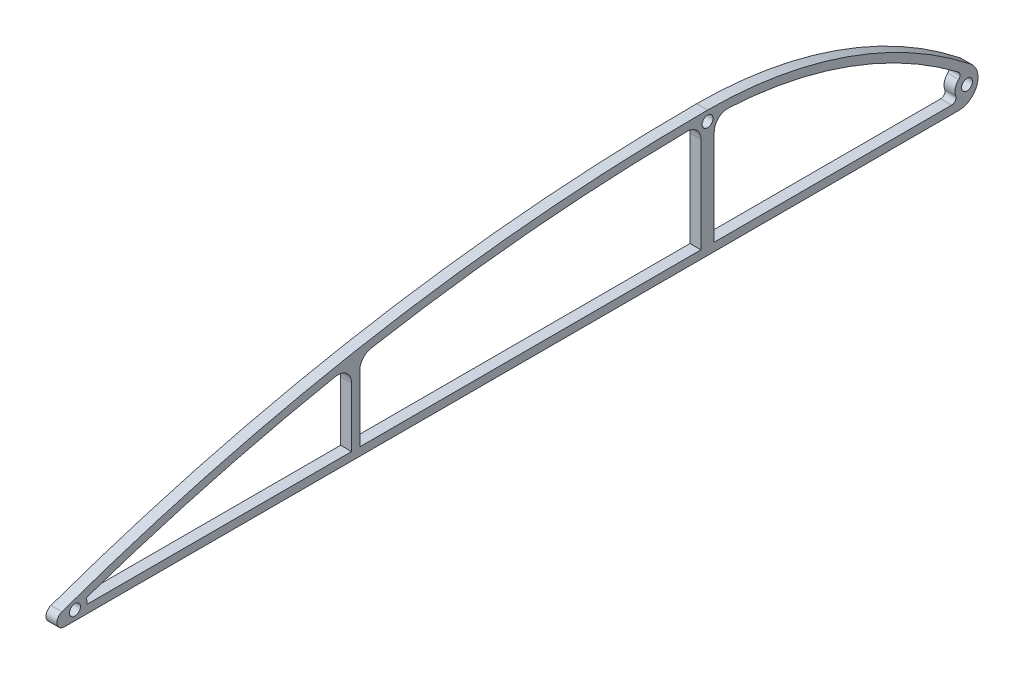
SolidWorks part; units mm, degrees
other "Marquage1"
sketch "Esquisse8" plane through (8, 0, -172.8424) normal (1, 0, 0) x (0, 0, -1)
other "Marquage2"
sketch "Esquisse10" plane through (-6, 20, -172.8424) normal (-0.8365, 0.2588, -0.483) x (-0.5, 0, 0.866)
other "Marquage3"
sketch "Esquisse11" plane through (0, 0, 0) normal (-0.0501, -0.1345, 0.9896) x (0.9942, 0.0873, 0.0622)
ref_plane "Plan de face" through (0, 0, 0) normal (0, 0, 1) x (1, 0, 0)
ref_plane "Plan de dessus" through (0, 0, 0) normal (0, 1, 0) x (1, 0, 0)
ref_plane "Plan de droite" through (0, 0, 0) normal (1, 0, 0) x (0, 0, -1)
sketch "Esquisse2" plane through (0, 0, 0) normal (1, 0, 0) x (0, 0, -1)
  line L0 (0, 0) -> (170.8732, 0)
  arc A1 (173.0499, 6.2408) -> (125, 23) centre (125, -54.2609) ccw
  arc A3 (170.8732, 0) -> (173.0499, 6.2408) centre (170.8732, 3.5) ccw
  arc A4 (125, 23) -> (0, 0) centre (125, -328.1739) ccw
  point P10 (180, 0)
  dimension "D1" = 180
  dimension "D2" = 3.5
  dimension "D3" = 23
  dimension "D4" = 55
extrude "Boss.-Extru.1" add sketch "Esquisse2" along normal blind 2
sketch "Esquisse4" plane through (2, 0, 0) normal (1, 0, 0) x (0, 0, -1)
  line L0 (9.5, 0) -> (9.5, 3.4627) construction
  line L1 (0, 0) -> (9.5, 1.7314) construction
  line L10 (174.369, 3.3283) -> (172.369, 3.3283) construction
  line L11 (0, 0) -> (170.8732, 0) construction
  circle A6 centre (125, 21.2) radius 1
  circle A12 centre (172.369, 3.3283) radius 1
  arc A13 (170.8732, 0) -> (173.0499, 6.2408) centre (170.8732, 3.5) ccw construction
  circle A15 centre (9.5, 1.7314) radius 1
  arc A16 (125, 23) -> (0, 0) centre (125, -328.1739) ccw construction
  dimension "D1" = 2
  dimension "D2" = 2
  dimension "D7" = 2
  dimension "D3" = 1.8
  dimension "D4" = 9.5
  dimension "D6" = 2
extrude "Enlèv. mat.-Extru.2" cut sketch "Esquisse4" against normal through all
sketch "Esquisse9" plane through (0, 0, 0) normal (1, 0, 0) x (0, 0, -1)
  line L26 (126.214, 1.5) -> (171.1454, 1.5)
  line L35 (8.4369, 1.5) -> (170.8732, 1.5)
  line L36 (11.6878, 1.5) -> (60, 1.5)
  line L40 (61.5, 1.5) -> (123.786, 1.5)
  line L42 (60, 1.5) -> (60, 15.4055)
  line L44 (61.5, 1.5) -> (61.5, 15.6859)
  line L45 (123.786, 21.4979) -> (123.786, 1.5)
  line L46 (126.214, 21.4979) -> (126.214, 1.5)
  arc A20 (60, 15.4055) -> (11.5307, 2.5776) centre (125, -328.1739) ccw
  circle A21 centre (125, 21.2) radius 1 construction
  circle A22 centre (9.5, 1.7314) radius 1 construction
  arc A23 (173.0499, 6.2408) -> (125, 23) centre (125, -54.2609) ccw construction
  arc A25 (171.6824, 5.4185) -> (171.1454, 1.5) centre (172.369, 3.3283) ccw
  circle A26 centre (172.369, 3.3283) radius 1 construction
  arc A35 (170.8732, 1.5) -> (172.117, 5.0662) centre (170.8732, 3.5) ccw
  arc A39 (172.117, 5.0662) -> (125, 21.5) centre (125, -54.2609) ccw
  arc A40 (125, 21.5) -> (8.4369, 1.5) centre (125, -328.1739) ccw
  arc A42 (171.6824, 5.4185) -> (126.214, 21.4979) centre (125, -54.2609) ccw
  arc A43 (123.786, 21.4979) -> (61.5, 15.6859) centre (125, -328.1739) ccw
  arc A54 (11.6878, 1.5) -> (11.5307, 2.5776) centre (9.5, 1.7314) ccw
  dimension "D1" = 1.5
  dimension "D2" = 1.25
  dimension "D3" = 1.2
  dimension "D5" = 1.25
  dimension "D4" = 1.2
  dimension "D6" = 1.5
  dimension "D7" = 60
extrude "Enlèv. mat.-Extru.3" cut sketch "Esquisse9" along normal blind 4
fillet "Congé2" radius 1.35 1 edges at (1, 0, 0)
fillet "Congé3" radius 2.5 4 edges at (1, 21.4979, -126.214) (1, 21.4979, -123.786) (1, 15.4055, -60) (1, 15.6859, -61.5)
fillet "Congé4" radius 0.8 2 edges at (1, 1.5, -171.1454) (1, 5.4185, -171.6824)
